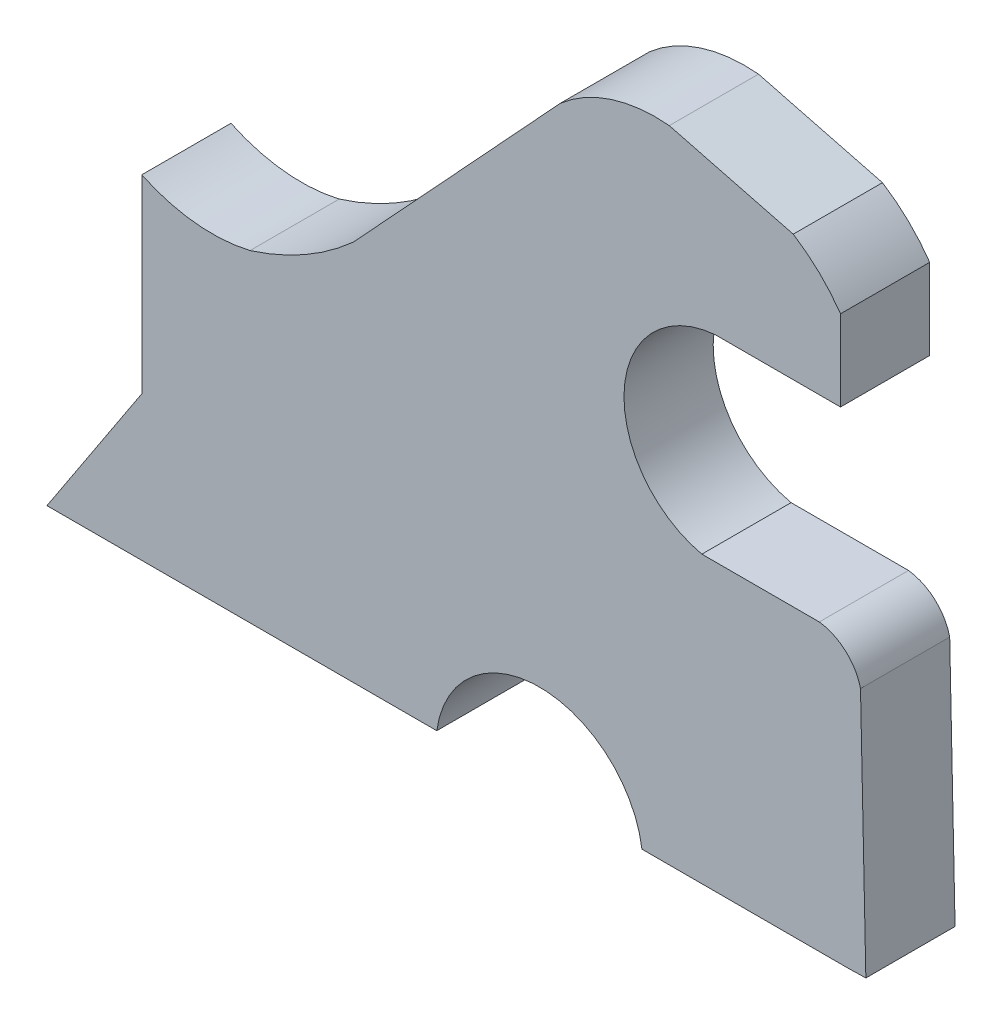
SolidWorks part; units mm, degrees
ref_plane "Ön Düzlem" through (0, 0, 0) normal (0, 0, 1) x (1, 0, 0)
ref_plane "Üst Düzlem" through (0, 0, 0) normal (0, 1, 0) x (1, 0, 0)
ref_plane "Sağ Düzlem" through (0, 0, 0) normal (1, 0, 0) x (0, 0, -1)
sketch "Çizim1" plane through (0, 0, 0) normal (0, 0, 1) x (1, 0, 0)
  line L0 (0, 0) -> (218.5, 0)
  line L1 (302.5, 50) -> (302.5, 0) construction
  line L2 (360, 0) -> (449, 0)
  line L3 (550.0826, 97.3608) -> (550.0826, 589.3608) construction
  line L4 (449, 0) -> (446, 139) construction
  line L5 (432.909, 160) -> (367.0814, 160)
  line L6 (374.5137, 275.2653) -> (436, 275.2653) construction
  line L7 (415.2252, 333.8789) -> (346.909, 351.5089) construction
  line L8 (171.8289, 213.8793) -> (287.7727, 339.2159)
  line L9 (53.1497, 187.1774) -> (53.1497, 80.8624)
  line L10 (0, 0) -> (53.1497, 80.8624)
  line L11 (333.5, 0) -> (360, 0)
  line L12 (374.5137, 270.2653) -> (434.7981, 270.2653)
  line L13 (374.5137, 270.2653) -> (436, 270.2653) construction
  line L14 (458.9977, 0.2158) -> (455.9977, 139.2158)
  line L15 (449, 0) -> (458.9977, 0.2158)
  line L16 (434.7981, 270.2653) -> (444.7981, 270.2653)
  line L17 (444.7981, 270.2653) -> (444.7981, 315.517)
  line L18 (418.3092, 340.932) -> (348.8081, 358.8678)
  line L20 (417.1243, 341.2378) -> (348.8081, 358.8678) construction
  arc A0 (245, 0) -> (360, 0) centre (302.5, -8.0625) cw construction
  arc A1 (446, 139) -> (420, 160) centre (419.4413, 132.713) ccw construction
  arc A2 (374.5137, 275.2653) -> (367.0814, 160) centre (379.3462, 217.0814) ccw construction
  arc A3 (434.7981, 270.2653) -> (440.201, 308.7194) centre (264.9649, 313.7338) ccw construction
  arc A4 (440.201, 308.7194) -> (415.2252, 333.8789) centre (368.7361, 262.7527) ccw construction
  arc A5 (346.909, 351.5089) -> (287.7727, 339.2159) centre (330.696, 281.1162) ccw construction
  arc A6 (113.8141, 180.7269) -> (171.8289, 213.8793) centre (67.1241, 329.7694) ccw
  arc A7 (53.1497, 187.1774) -> (113.8141, 180.7269) centre (92.6596, 270.2653) ccw
  arc A8 (218.5, 0) -> (333.5, 0) centre (276, -8.0625) cw
  arc A9 (374.5137, 270.2653) -> (367.0814, 160) centre (379.3462, 214.5564) ccw
  arc A10 (455.9977, 139.2158) -> (432.909, 160) centre (429.4389, 132.9288) ccw
  arc A11 (444.7981, 315.517) -> (418.3092, 340.932) centre (368.7361, 262.7527) ccw
  arc A12 (446.5929, 312.8308) -> (419.3833, 340.2405) centre (368.7361, 262.7527) ccw construction
  arc A13 (287.7727, 339.2159) -> (348.8081, 358.8678) centre (341.1816, 277.9456) cw
  point P10 (360, 162)
  point P11 (357, 271)
  dimension "D15" = 146.5
  dimension "D18" = 115
  dimension "D20" = 58.3842
  dimension "D23" = 10
  dimension "D1" = 245
  dimension "D2" = 360
  dimension "D3" = 50
  dimension "D4" = 449
  dimension "D5" = 139
  dimension "D6" = 420
  dimension "D7" = 446
  dimension "D8" = 160
  dimension "D9" = 162
  dimension "D10" = 360
  dimension "D11" = 271
  dimension "D12" = 357
  dimension "D13" = 275.2653
  dimension "D14" = 436
  dimension "D17" = 173
  dimension "D19" = 5
  dimension "D21" = 58.6136
  dimension "D22" = 63.6136
  dimension "D24" = 10
  dimension "D25" = 7.6
  dimension "D26" = 7.6
  dimension "D16" = 2
base flange "Taban-Flanş1" sketch "Çizim1" thickness 50 reverse thickness direction yes parameters "D1"=10
sketch "Büküm-Çizgileri1" [suppressed] plane through (0, 0, 0) normal (0, 1, 0) x (1, 0, 0)
sketch "Sınırlandırma-Kutusu1" [suppressed] plane through (0, 0, 0) normal (0, 1, 0) x (1, 0, 0)
sheet metal parameters "Sac-Levha1" thickness 50 parameters "D1"=10
flat pattern "Düz-Çoğaltma1" [suppressed]
sketch "Büküm-Çizgileri2" plane through (0, 0, 0) normal (0, 1, 0) x (1, 0, 0)
sketch3d "Sınırlandırma-Kutusu2" [suppressed]
  line L0 (92.6596, -270.2653, 0) -> (-366.3381, -270.2653, 0) construction
  line L1 (92.6596, 88.961, 0) -> (-366.3381, 88.961, 0) construction
  line L2 (92.6596, -270.2653, 0) -> (92.6596, 88.961, 0) construction
  line L3 (-366.3381, -270.2653, 0) -> (-366.3381, 88.961, 0) construction
